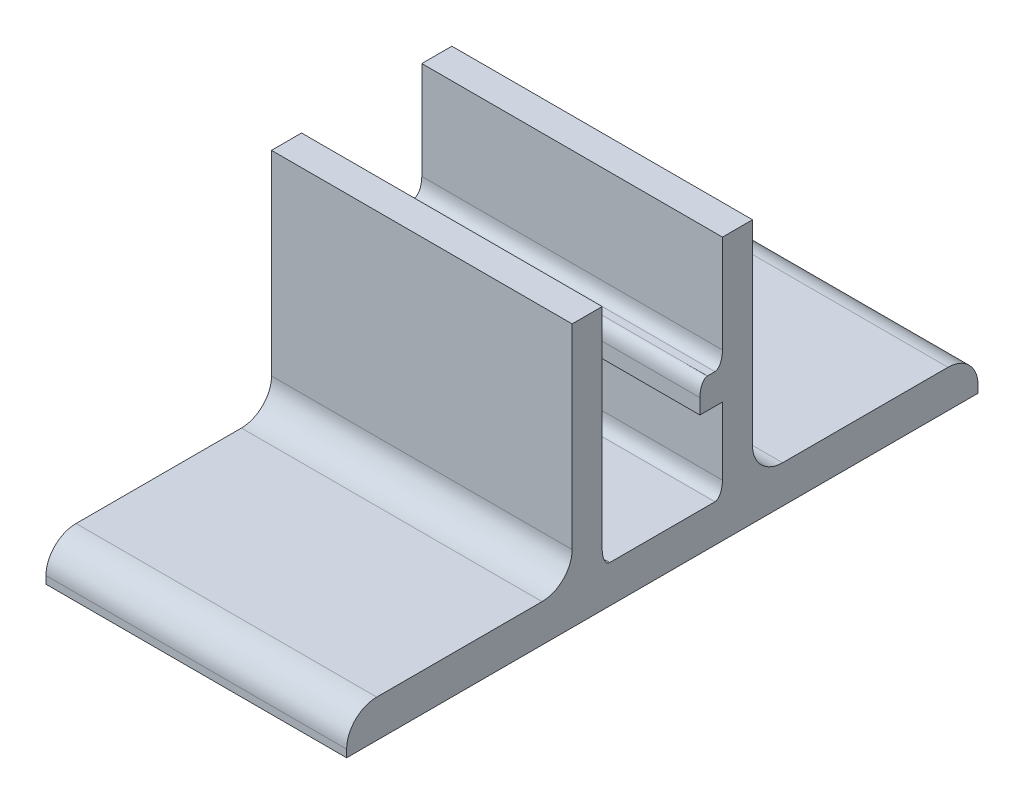
SolidWorks part; units mm, degrees
ref_plane "Front Plane" through (0, 0, 0) normal (0, 0, 1) x (1, 0, 0)
ref_plane "Top Plane" through (0, 0, 0) normal (0, 1, 0) x (1, 0, 0)
ref_plane "Right Plane" through (0, 0, 0) normal (1, 0, 0) x (0, 0, -1)
sketch "Sketch1" plane through (0, 0, 0) normal (1, 0, 0) x (0, 0, -1)
  line L0 (0, 0) -> (106.68, 0)
  line L1 (106.68, 0) -> (106.68, 6.35)
  line L6 (0, 6.35) -> (0, 0)
  line L7 (43.18, 44.45) -> (43.18, 6.35)
  line L8 (43.18, 6.35) -> (63.5, 6.35)
  line L9 (63.5, 6.35) -> (63.5, 44.45)
  line L10 (0, 6.35) -> (38.1, 6.35)
  line L11 (38.1, 6.35) -> (38.1, 44.45)
  line L12 (38.1, 44.45) -> (43.18, 44.45)
  line L13 (63.5, 44.45) -> (68.58, 44.45)
  line L14 (68.58, 44.45) -> (68.58, 6.35)
  line L15 (68.58, 6.35) -> (106.68, 6.35)
  point P12 (20.8121, 44.45)
  point P15 (0, 0)
  dimension "D1" = 5.08
  dimension "D2" = 38.1
  dimension "D3" = 6.35
  dimension "D4" = 38.1
  dimension "D5" = 20.32
  dimension "D6" = 38.1
extrude "Boss-Extrude1" add sketch "Sketch1" along normal blind 50.8
sketch "Sketch2" plane through (0, 0, 0) normal (-1, 0, 0) x (0, 0, 1)
  line L0 (-43.18, 6.35) -> (-43.18, 44.45) construction
  line L1 (-63.5, 6.35) -> (-43.18, 6.35)
  line L2 (-63.5, 6.35) -> (-63.5, 44.45)
  line L3 (-63.5, 44.45) -> (-43.18, 44.45)
  line L4 (-43.18, 6.35) -> (-43.18, 44.45)
  point P9 (0, 0)
  point P11 (0, 0)
extrude "Boss-Extrude2" [suppressed] add sketch "Sketch2" against normal blind 2.54
sketch "Sketch4" plane through (50.8, 0, 0) normal (1, 0, 0) x (0, 0, -1)
  line L0 (63.5, 44.45) -> (63.5, 6.35) construction
  line L1 (63.5, 20.32) -> (59.69, 20.32)
  line L2 (63.5, 20.32) -> (63.5, 25.4)
  line L3 (63.5, 25.4) -> (59.69, 25.4)
  line L4 (59.69, 20.32) -> (59.69, 25.4)
  line L5 (63.5, 6.35) -> (43.18, 6.35) construction
  dimension "D1" = 3.81
  dimension "D2" = 13.97
  dimension "D3" = 5.08
extrude "Boss-Extrude5" add sketch "Sketch4" against normal blind 50.8
fillet "Fillet1" radius 5.08 4 edges at (25.4, 6.35, -106.68) (25.4, 6.35, 0) (25.4, 6.35, -38.1) (25.4, 6.35, -68.58)
fillet "Fillet2" radius 1.27 4 edges at (25.4, 6.35, -63.5) (25.4, 6.35, -43.18) (25.4, 25.4, -63.5) (25.4, 25.4, -59.69)
